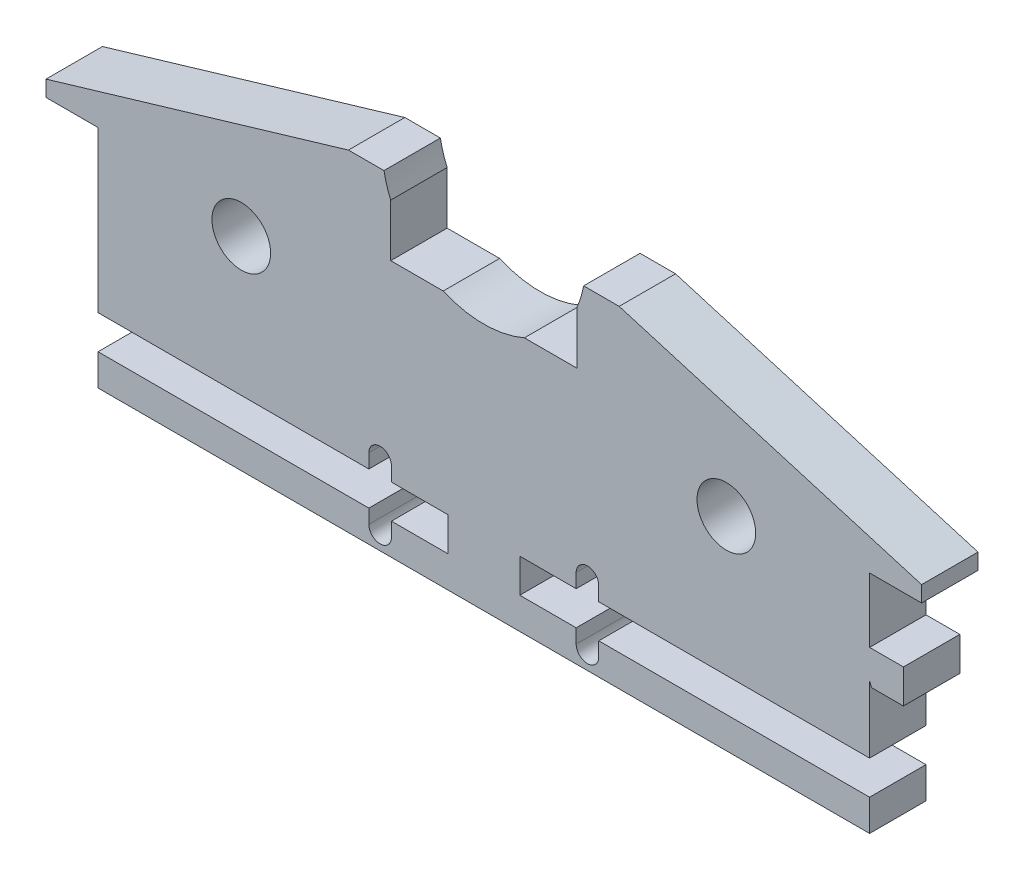
SolidWorks part; units mm, degrees
ref_plane "Front Plane" through (0, 0, 0) normal (0, 0, 1) x (1, 0, 0)
ref_plane "Top Plane" through (0, 0, 0) normal (0, 1, 0) x (1, 0, 0)
ref_plane "Right Plane" through (0, 0, 0) normal (1, 0, 0) x (0, 0, -1)
sketch "Sketch1" plane through (0, 0, 0) normal (0, 0, 1) x (1, 0, 0)
  line L0 (21.3889, -7.2015) -> (21.3889, -10.2015)
  line L1 (-47.0091, -18.4873) -> (21.3889, -18.4873)
  line L2 (-26, -14.2015) -> (26, -14.2015) construction
  line L3 (21.3889, 1.5127) -> (21.3889, -4.2015)
  line L4 (21.3889, 1.5127) -> (26, 1.5127)
  line L5 (-47.0091, -16.9615) -> (16.1812, 5.8384) construction
  line L6 (-15.7126, 13.581) -> (21.3889, -18.4873) construction
  line L7 (-4.5601, 4.2627) -> (-9.2132, 4.2627)
  line L8 (-4.5601, 4.2627) -> (-4.5601, 8.9159)
  line L9 (-4.5601, 20.7627) -> (-9.2132, 20.7627)
  line L10 (-21.0601, 4.2627) -> (-21.0601, 8.9159)
  line L11 (-4.5601, 4.2627) -> (-21.0601, 20.7627) construction
  line L12 (-4.5601, 20.7627) -> (-21.0601, 4.2627) construction
  line L13 (26, 2.9244) -> (-0.8101, 10.8811)
  line L14 (-0.8101, 10.8811) -> (-24.8101, 10.8811)
  line L15 (-24.8101, 10.8811) -> (-51.6202, 2.9244)
  line L16 (-12.8101, 10.8811) -> (-12.8101, 12.5127) construction
  line L17 (-16.407, 20.7627) -> (-21.0601, 20.7627)
  line L18 (26, 1.5127) -> (26, 2.9244)
  line L19 (-21.0601, 16.1096) -> (-21.0601, 20.7627)
  line L20 (21.3889, -10.2015) -> (26, -10.2015)
  line L21 (21.3889, -6.773) -> (26, -18.2015)
  line L22 (-47.0091, -6.773) -> (-47.0091, -18.4873)
  line L23 (-22, -11.4515) -> (-22, -16.9515) construction
  line L24 (21.3889, -6.773) -> (21.3889, -18.4873)
  line L25 (26, -10.2015) -> (26, -12.7015)
  line L26 (-47.0091, -6.773) -> (-51.6202, -18.2015)
  line L27 (-51.6202, -10.2015) -> (-51.6202, -12.7015)
  line L28 (-47.0091, -10.2015) -> (-51.6202, -10.2015)
  line L29 (-51.6202, 1.5127) -> (-51.6202, 2.9244)
  line L30 (-47.0091, 1.5127) -> (-47.0091, -10.2015)
  line L31 (-47.0091, 1.5127) -> (-51.6202, 1.5127)
  line L32 (-51.6202, -15.7015) -> (-23, -15.7015)
  line L33 (-51.6202, -12.7015) -> (-23, -12.7015)
  line L34 (-16.407, 4.2627) -> (-21.0601, 4.2627)
  line L35 (19.1899, -18.4873) -> (-44.8101, -18.4873) construction
  line L36 (-21, -11.4515) -> (-21, -12.7015)
  line L37 (-23, -11.4515) -> (-23, -12.7015)
  line L38 (-16, -12.7015) -> (-16, -15.7015)
  line L39 (-4.5601, 16.1096) -> (-4.5601, 20.7627)
  line L40 (-23, -15.7015) -> (-23, -16.9515)
  line L41 (-21, -15.7015) -> (-21, -16.9515)
  line L42 (-21, -12.7015) -> (-16, -12.7015)
  line L43 (-21, -15.7015) -> (-16, -15.7015)
  line L44 (-51.6202, -15.7015) -> (-51.6202, -18.2015)
  line L45 (-3.6202, -11.4515) -> (-3.6202, -16.9515) construction
  line L46 (-4.6202, -15.7015) -> (-9.6202, -15.7015)
  line L47 (-4.6202, -12.7015) -> (-9.6202, -12.7015)
  line L48 (-4.6202, -15.7015) -> (-4.6202, -16.9515)
  line L49 (-2.6202, -15.7015) -> (-2.6202, -16.9515)
  line L50 (-9.6202, -12.7015) -> (-9.6202, -15.7015)
  line L51 (-2.6202, -11.4515) -> (-2.6202, -12.7015)
  line L52 (-4.6202, -11.4515) -> (-4.6202, -12.7015)
  line L53 (26, -12.7015) -> (-2.6202, -12.7015)
  line L54 (26, -15.7015) -> (-2.6202, -15.7015)
  line L55 (26, -15.7015) -> (26, -18.2015)
  line L56 (21.3889, -7.2015) -> (24.3889, -7.2015)
  line L58 (21.3889, -4.2015) -> (24.3889, -4.2015)
  line L59 (24.3889, -7.2015) -> (24.3889, -4.2015)
  circle A0 centre (8.6899, -0.4873) radius 2.6
  circle A1 centre (-34.3101, -0.4873) radius 2.6
  arc A2 (-21, -11.4515) -> (-23, -11.4515) centre (-22, -11.4515) ccw
  arc A3 (-23, -16.9515) -> (-21, -16.9515) centre (-22, -16.9515) ccw
  arc A4 (-2.6202, -16.9515) -> (-4.6202, -16.9515) centre (-3.6202, -16.9515) cw
  arc A5 (-4.6202, -11.4515) -> (-2.6202, -11.4515) centre (-3.6202, -11.4515) cw
  arc A6 (-9.2132, 20.7627) -> (-16.407, 20.7627) centre (-12.8101, 12.5127) ccw
  arc A7 (-4.5601, 16.1096) -> (-9.2132, 20.7627) centre (-12.8101, 12.5127) ccw construction
  arc A8 (-3.9351, 11.018) -> (-3.9351, 14.0075) centre (-4.0601, 12.5127) ccw
  arc A9 (-21.6851, 14.0075) -> (-21.6851, 11.018) centre (-21.5601, 12.5127) ccw
  arc A10 (-3.9351, 11.018) -> (-3.9351, 14.0075) centre (-4.0601, 12.5127) ccw construction
  arc A11 (-21.6851, 14.0075) -> (-21.6851, 11.018) centre (-21.5601, 12.5127) ccw construction
  arc A12 (-21.0601, 16.1096) -> (-21.0601, 8.9159) centre (-12.8101, 12.5127) ccw
  arc A13 (-16.407, 4.2627) -> (-9.2132, 4.2627) centre (-12.8101, 12.5127) ccw
  arc A14 (-4.5601, 8.9159) -> (-3.9351, 11.018) centre (-12.8101, 12.5127) ccw
  arc A15 (-3.9351, 14.0075) -> (-4.5601, 16.1096) centre (-12.8101, 12.5127) ccw
  point P0 (0, 0)
  point P6 (-12.8101, 12.5127)
  point P52 (-22, -14.2015)
  point P80 (-3.6202, -14.2015)
  dimension "D2" = 5.2
  dimension "D1" = 3
  dimension "D3" = 24
  dimension "D8" = 5.5
  dimension "D9" = 2
  dimension "D4" = 3
  dimension "D5" = 3
extrude "Boss-Extrude1" add sketch "Sketch1" along normal blind 5 contours L52 A5 L51 L53 L25 L20 L3 L4 L18 L13 L14 L15 L29 L31 L30 L28 L27 L33 L37 A2 L36 L42 L38 L43 L41 A3 L40 L32 L44 L26 L22 L1 L24 L21 L55 L54 L49 A4 L48 L46 L50 L47 A15 A8 A14 L8 L7 A13 L34 L10 region at (-12.6012, -4.4857, 0)
sketch "Sketch2" [suppressed] plane through (0, 0, 5) normal (0, 0, 1) x (1, 0, 0)
  line L0 (-16, -14.2015) -> (16, -14.2015) construction
  line L4 (-28, -30.7015) -> (28, -30.7015)
  line L5 (-28, -30.7015) -> (-28, 2.2985)
  line L6 (-28, 2.2985) -> (28, 2.2985)
  line L7 (28, -30.7015) -> (28, 2.2985)
  line L8 (-28, -30.7015) -> (28, 2.2985) construction
  line L9 (-28, 2.2985) -> (28, -30.7015) construction
  line L11 (-29.6774, -33.6457) -> (40.0725, -33.6457)
  line L12 (-29.6774, -33.6457) -> (-29.6774, 19.8189)
  line L13 (-29.6774, 19.8189) -> (40.0725, 19.8189)
  line L14 (40.0725, -33.6457) -> (40.0725, 19.8189)
  circle A0 centre (0, -14.2015) radius 13.5
  dimension "D1" = 27
  dimension "D2" = 33
extrude "Cut-Extrude1" [suppressed] cut sketch "Sketch2" against normal blind 10 contours A0 | L11 L14 L13 L12 L7 L4 L5 L6
sketch "Sketch3" [suppressed] plane through (0, 0, 0) normal (0, 0, -1) x (-1, 0, 0)
  line L0 (28, -4.2015) -> (28, -10.2015) construction
  line L1 (-26, -0.7015) -> (-8.25, -0.7015)
  line L2 (-28.2413, -0.7015) -> (-28.2413, 4.2985)
  line L3 (-28.2413, 4.2985) -> (28, 4.2985)
  line L4 (28, -0.7015) -> (28, 4.2985)
  line L5 (8.25, -1.4515) -> (8.25, 2.2985) construction
  line L6 (-28, -27.7015) -> (28, -27.7015) construction
  line L7 (-8.25, -0.7015) -> (-8.25, -3.5156)
  line L8 (8.25, -0.7015) -> (26, -0.7015)
  line L9 (8.25, -0.7015) -> (8.25, -3.5156)
  line L10 (-8.25, -1.4515) -> (-8.25, 2.2985) construction
  line L11 (-28, -24.2015) -> (28, -24.2015)
  line L12 (-28, -24.2015) -> (-28, -32.7015)
  line L13 (-28, -32.7015) -> (28, -32.7015)
  line L14 (28, -24.2015) -> (28, -32.7015)
  line L15 (26, -4.2015) -> (26, 2.2985) construction
  line L17 (-28.2413, -0.7015) -> (-28.2413, -4.2015)
  line L18 (-28.2413, -4.2015) -> (-26, -4.2015)
  line L19 (-26, -0.7015) -> (-26, -4.2015)
  line L20 (28, -4.2015) -> (26, -4.2015)
  line L21 (28, -4.2015) -> (28, -0.7015)
  line L23 (26, -4.2015) -> (26, -0.7015)
  circle A0 centre (0, -14.2015) radius 13.5
  arc A1 (-4.4371, -1.4515) -> (-9.0692, -24.2015) centre (0, -14.2015) ccw construction
  line M1 (-8.25, -1.4515) -> (-8.25, 2.2985)
  line M2 (-8.25, 2.2985) -> (-26, 2.2985)
  line M3 (-26, 2.2985) -> (-26, -4.2015)
  line M4 (-26, -4.2015) -> (-28, -4.2015)
  line M22 (-28, -24.2015) -> (-9.0692, -24.2015)
  line M24 (-4.4371, -1.4515) -> (-8.25, -1.4515)
  dimension "D1" = 5
  dimension "D2" = 5
extrude "Boss-Extrude2" [suppressed] add sketch "Sketch3" against normal blind 5 contours A0 L9 L8 L23 L20 L21 L4 L3 L2 L17 L18 M4 M3 M2 M1 M24 | L6 L12 L13 L14 | A0 L6 L14 L11 | L12 L6 A0 M22
